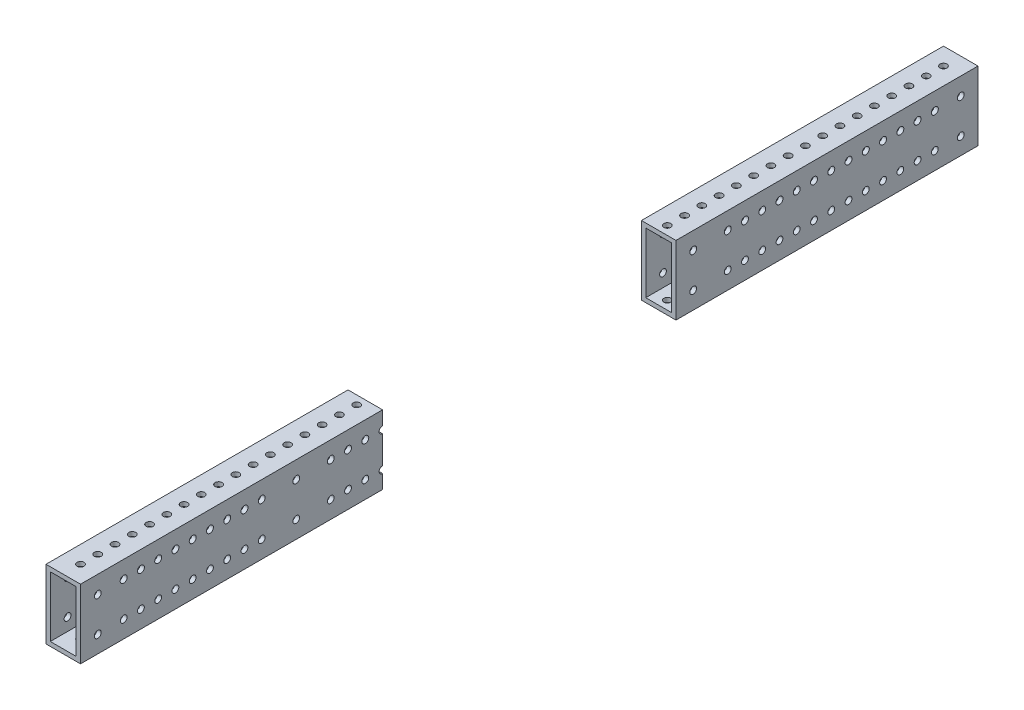
SolidWorks part; units mm, degrees
material "6061-T6 (SS)"
ref_plane "Front Plane" through (0, 0, 0) normal (0, 0, 1) x (1, 0, 0)
ref_plane "Top Plane" through (0, 0, 0) normal (0, 1, 0) x (1, 0, 0)
ref_plane "Right Plane" through (0, 0, 0) normal (1, 0, 0) x (0, 0, -1)
sketch "Sketch1" plane through (0, 0, 0) normal (0, 0, 1) x (1, 0, 0)
  line L0 (-9.525, 22.225) -> (9.525, 22.225)
  line L1 (-12.7, 25.4) -> (12.7, 25.4)
  line L2 (-12.7, 25.4) -> (-12.7, -25.4)
  line L3 (-12.7, -25.4) -> (12.7, -25.4)
  line L4 (12.7, 25.4) -> (12.7, -25.4)
  line L5 (9.525, 22.225) -> (9.525, -22.225)
  line L6 (-9.525, -22.225) -> (9.525, -22.225)
  line L7 (-9.525, 22.225) -> (-9.525, -22.225)
  line L8 (-12.7, 25.4) -> (12.7, -25.4) construction
  line L9 (12.7, 25.4) -> (-12.7, -25.4) construction
  point P5 (0, 0)
  dimension "D1" = 25.4
  dimension "D2" = 50.8
  dimension "D3" = 3.175
extrude "Boss-Extrude1" add sketch "Sketch1" along normal mid plane 660.4
sketch "Sketch2" plane through (0, 25.4, 0) normal (0, 1, 0) x (1, 0, 0)
  line L0 (12.7, -330.2) -> (-12.7, -330.2) construction
  line L1 (-12.7, -330.2) -> (-12.7, 330.2) construction
  line L4 (12.7, 330.2) -> (-12.7, 330.2) construction
  circle A0 centre (0, -317.5) radius 2.5527 construction
  circle A1 centre (25.4, -292.1) radius 2.5527 construction
  circle A2 centre (0, -317.5) radius 2.5527
  circle A3 centre (0, -304.8) radius 2.5527
  circle A4 centre (0, -304.8) radius 2.5527 construction
  circle A5 centre (25.4, -279.4) radius 2.5527 construction
  circle A6 centre (0, -292.1) radius 2.5527
  circle A7 centre (0, -292.1) radius 2.5527 construction
  circle A8 centre (25.4, -266.7) radius 2.5527 construction
  circle A9 centre (0, -279.4) radius 2.5527
  circle A10 centre (0, -279.4) radius 2.5527 construction
  circle A11 centre (25.4, -254) radius 2.5527 construction
  circle A12 centre (0, -266.7) radius 2.5527
  circle A13 centre (0, -266.7) radius 2.5527 construction
  circle A14 centre (25.4, -241.3) radius 2.5527 construction
  circle A15 centre (0, -254) radius 2.5527
  circle A16 centre (0, -254) radius 2.5527 construction
  circle A17 centre (25.4, -228.6) radius 2.5527 construction
  circle A18 centre (0, -241.3) radius 2.5527
  circle A19 centre (0, -241.3) radius 2.5527 construction
  circle A20 centre (25.4, -215.9) radius 2.5527 construction
  circle A21 centre (0, -228.6) radius 2.5527
  circle A22 centre (0, -228.6) radius 2.5527 construction
  circle A23 centre (25.4, -203.2) radius 2.5527 construction
  circle A24 centre (0, -215.9) radius 2.5527
  circle A25 centre (0, -215.9) radius 2.5527 construction
  circle A26 centre (25.4, -190.5) radius 2.5527 construction
  circle A27 centre (0, -203.2) radius 2.5527
  circle A28 centre (0, -203.2) radius 2.5527 construction
  circle A29 centre (25.4, -177.8) radius 2.5527 construction
  circle A30 centre (0, -190.5) radius 2.5527
  circle A31 centre (0, -190.5) radius 2.5527 construction
  circle A32 centre (25.4, -165.1) radius 2.5527 construction
  circle A33 centre (0, -177.8) radius 2.5527
  circle A34 centre (0, -177.8) radius 2.5527 construction
  circle A35 centre (25.4, -152.4) radius 2.5527 construction
  circle A36 centre (0, -165.1) radius 2.5527
  circle A37 centre (0, -165.1) radius 2.5527 construction
  circle A38 centre (25.4, -139.7) radius 2.5527 construction
  circle A39 centre (0, -152.4) radius 2.5527
  circle A40 centre (0, -152.4) radius 2.5527 construction
  circle A41 centre (25.4, -127) radius 2.5527 construction
  circle A42 centre (0, -139.7) radius 2.5527
  circle A43 centre (0, -139.7) radius 2.5527 construction
  circle A44 centre (25.4, -114.3) radius 2.5527 construction
  circle A45 centre (0, -127) radius 2.5527
  circle A46 centre (0, -127) radius 2.5527 construction
  circle A47 centre (25.4, -101.6) radius 2.5527 construction
  circle A48 centre (0, -114.3) radius 2.5527
  circle A49 centre (0, -114.3) radius 2.5527 construction
  circle A50 centre (25.4, -88.9) radius 2.5527 construction
  circle A51 centre (0, -101.6) radius 2.5527
  circle A52 centre (0, -101.6) radius 2.5527 construction
  circle A53 centre (25.4, -76.2) radius 2.5527 construction
  circle A54 centre (0, -88.9) radius 2.5527
  circle A55 centre (0, -88.9) radius 2.5527 construction
  circle A56 centre (25.4, -63.5) radius 2.5527 construction
  circle A57 centre (0, -76.2) radius 2.5527
  circle A58 centre (0, -76.2) radius 2.5527 construction
  circle A59 centre (25.4, -50.8) radius 2.5527 construction
  circle A60 centre (0, -63.5) radius 2.5527
  circle A61 centre (0, -63.5) radius 2.5527 construction
  circle A62 centre (25.4, -38.1) radius 2.5527 construction
  circle A63 centre (0, -50.8) radius 2.5527
  circle A64 centre (0, -50.8) radius 2.5527 construction
  circle A65 centre (25.4, -25.4) radius 2.5527 construction
  circle A66 centre (0, -38.1) radius 2.5527
  circle A67 centre (0, -38.1) radius 2.5527 construction
  circle A68 centre (25.4, -12.7) radius 2.5527 construction
  circle A69 centre (0, -25.4) radius 2.5527
  circle A70 centre (0, -25.4) radius 2.5527 construction
  circle A71 centre (25.4, 0) radius 2.5527 construction
  circle A72 centre (0, -12.7) radius 2.5527
  circle A73 centre (0, -12.7) radius 2.5527 construction
  circle A74 centre (25.4, 12.7) radius 2.5527 construction
  circle A75 centre (0, 0) radius 2.5527
  circle A76 centre (0, 0) radius 2.5527 construction
  circle A77 centre (25.4, 25.4) radius 2.5527 construction
  circle A78 centre (0, 12.7) radius 2.5527
  circle A79 centre (0, 12.7) radius 2.5527 construction
  circle A80 centre (25.4, 38.1) radius 2.5527 construction
  circle A81 centre (0, 25.4) radius 2.5527
  circle A82 centre (0, 25.4) radius 2.5527 construction
  circle A83 centre (25.4, 50.8) radius 2.5527 construction
  circle A84 centre (0, 38.1) radius 2.5527
  circle A85 centre (0, 38.1) radius 2.5527 construction
  circle A86 centre (25.4, 63.5) radius 2.5527 construction
  circle A87 centre (0, 50.8) radius 2.5527
  circle A88 centre (0, 50.8) radius 2.5527 construction
  circle A89 centre (25.4, 76.2) radius 2.5527 construction
  circle A90 centre (0, 63.5) radius 2.5527
  circle A91 centre (0, 63.5) radius 2.5527 construction
  circle A92 centre (25.4, 88.9) radius 2.5527 construction
  circle A93 centre (0, 76.2) radius 2.5527
  circle A94 centre (0, 76.2) radius 2.5527 construction
  circle A95 centre (25.4, 101.6) radius 2.5527 construction
  circle A96 centre (0, 88.9) radius 2.5527
  circle A97 centre (0, 88.9) radius 2.5527 construction
  circle A98 centre (25.4, 114.3) radius 2.5527 construction
  circle A99 centre (0, 101.6) radius 2.5527
  circle A100 centre (0, 101.6) radius 2.5527 construction
  circle A101 centre (25.4, 127) radius 2.5527 construction
  circle A108 centre (0, 127) radius 2.5527 [skipped]
  circle A109 centre (0, 127) radius 2.5527 [skipped]
  circle A110 centre (25.4, 152.4) radius 2.5527 [skipped]
  circle A111 centre (0, 114.3) radius 2.5527 [skipped]
  circle A112 centre (0, 114.3) radius 2.5527 [skipped]
  circle A113 centre (25.4, 139.7) radius 2.5527 [skipped]
  circle A114 centre (25.4, 139.7) radius 2.5527 construction
  circle A115 centre (0, 114.3) radius 2.5527 construction
  circle A116 centre (0, 114.3) radius 2.5527
  circle A117 centre (25.4, 152.4) radius 2.5527 construction
  circle A118 centre (0, 127) radius 2.5527 construction
  circle A119 centre (0, 127) radius 2.5527
  circle A120 centre (25.4, 165.1) radius 2.5527 construction
  circle A121 centre (0, 139.7) radius 2.5527 construction
  circle A122 centre (0, 139.7) radius 2.5527
  circle A123 centre (25.4, 177.8) radius 2.5527 construction
  circle A124 centre (0, 152.4) radius 2.5527 construction
  circle A125 centre (0, 152.4) radius 2.5527
  circle A126 centre (25.4, 190.5) radius 2.5527 construction
  circle A127 centre (0, 165.1) radius 2.5527 construction
  circle A128 centre (0, 165.1) radius 2.5527
  circle A129 centre (25.4, 203.2) radius 2.5527 construction
  circle A130 centre (0, 177.8) radius 2.5527 construction
  circle A131 centre (0, 177.8) radius 2.5527
  circle A132 centre (25.4, 215.9) radius 2.5527 construction
  circle A133 centre (0, 190.5) radius 2.5527 construction
  circle A134 centre (0, 190.5) radius 2.5527
  circle A135 centre (25.4, 228.6) radius 2.5527 construction
  circle A136 centre (0, 203.2) radius 2.5527 construction
  circle A137 centre (0, 203.2) radius 2.5527
  circle A138 centre (25.4, 241.3) radius 2.5527 construction
  circle A139 centre (0, 215.9) radius 2.5527 construction
  circle A140 centre (0, 215.9) radius 2.5527
  circle A141 centre (25.4, 254) radius 2.5527 construction
  circle A142 centre (0, 228.6) radius 2.5527 construction
  circle A143 centre (0, 228.6) radius 2.5527
  circle A144 centre (25.4, 266.7) radius 2.5527 construction
  circle A145 centre (0, 241.3) radius 2.5527 construction
  circle A146 centre (0, 241.3) radius 2.5527
  circle A147 centre (25.4, 279.4) radius 2.5527 construction
  circle A148 centre (0, 254) radius 2.5527 construction
  circle A149 centre (0, 254) radius 2.5527
  circle A150 centre (25.4, 292.1) radius 2.5527 construction
  circle A151 centre (0, 266.7) radius 2.5527 construction
  circle A152 centre (0, 266.7) radius 2.5527
  circle A153 centre (0, 279.4) radius 2.5527
  circle A154 centre (0, 292.1) radius 2.5527
  circle A155 centre (0, 304.8) radius 2.5527
  circle A156 centre (0, 317.5) radius 2.5527
  dimension "D2" = 5.1054
  dimension "D4" = 12.7
  dimension "D9" = 12.7
  dimension "D11" = 12.7
  dimension "D12" = 12.7
  dimension "D1" = 12.7
  dimension "D3" = 12.7
  dimension "D6" = 12.7
  dimension "D7" = 228.6
  dimension "D5" = 36
  dimension "D8" = 14
  dimension "D10" = 5
extrude "Cut-Extrude1" cut sketch "Sketch2" against normal through all
sketch "Sketch4" plane through (12.7, 0, 0) normal (1, 0, 0) x (0, 0, -1)
  line L0 (-330.2, 25.4) -> (330.2, 25.4) construction
  line L1 (-330.2, -25.4) -> (-330.2, 25.4) construction
  line L2 (-330.2, -25.4) -> (330.2, -25.4) construction
  line L3 (-330.2, 25.4) -> (-330.2, -25.4) construction
  line L4 (-134.0934, 25.4) -> (-328.1801, 25.4) construction
  line L5 (-330.2, 25.4) -> (330.2, 25.4) construction
  line L6 (330.2, -25.4) -> (330.2, 25.4) construction
  circle A2 centre (-323.85, -12.7) radius 2.4892 construction
  circle A3 centre (-311.15, -12.7) radius 2.4892 construction
  circle A16 centre (-298.45, -12.7) radius 2.4892
  circle A17 centre (-285.75, -12.7) radius 2.4892
  circle A18 centre (-273.05, -12.7) radius 2.4892
  circle A19 centre (107.95, -12.7) radius 2.4892 construction
  circle A20 centre (120.65, -12.7) radius 2.4892
  circle A21 centre (133.35, -12.7) radius 2.4892 construction
  circle A22 centre (146.05, -12.7) radius 2.4892
  circle A23 centre (158.75, -12.7) radius 2.4892
  circle A24 centre (171.45, -12.7) radius 2.4892
  circle A25 centre (184.15, -12.7) radius 2.4892
  circle A26 centre (196.85, -12.7) radius 2.4892
  circle A27 centre (209.55, -12.7) radius 2.4892
  circle A28 centre (222.25, -12.7) radius 2.4892
  circle A29 centre (234.95, -12.7) radius 2.4892
  circle A30 centre (247.65, -12.7) radius 2.4892
  circle A31 centre (260.35, -12.7) radius 2.4892
  circle A32 centre (273.05, -12.7) radius 2.4892
  circle A33 centre (-323.85, 12.7) radius 2.5527 construction
  circle A34 centre (-311.15, 12.7) radius 2.5527 construction
  circle A35 centre (-260.35, -12.7) radius 2.4892
  circle A36 centre (-247.65, -12.7) radius 2.4892
  circle A37 centre (-234.95, -12.7) radius 2.4892
  circle A38 centre (-222.25, -12.7) radius 2.4892
  circle A39 centre (-209.55, -12.7) radius 2.4892
  circle A40 centre (-196.85, -12.7) radius 2.4892
  circle A41 centre (-184.15, -12.7) radius 2.4892 construction
  circle A42 centre (-171.45, -12.7) radius 2.4892
  circle A43 centre (-158.75, -12.7) radius 2.4892 construction
  circle A44 centre (-146.05, -12.7) radius 2.4892
  circle A45 centre (-133.35, -12.7) radius 2.4892
  circle A46 centre (-120.65, -12.7) radius 2.4892
  circle A47 centre (-107.95, -12.7) radius 2.4892
  circle A48 centre (-95.25, -12.7) radius 2.4892
  circle A49 centre (-82.55, -12.7) radius 2.4892
  circle A50 centre (-69.85, -12.7) radius 2.4892
  circle A51 centre (-57.15, -12.7) radius 2.4892
  circle A52 centre (-44.45, -12.7) radius 2.4892
  circle A53 centre (-31.75, -12.7) radius 2.4892
  circle A54 centre (-19.05, -12.7) radius 2.4892
  circle A55 centre (-6.35, -12.7) radius 2.4892
  circle A56 centre (6.35, -12.7) radius 2.4892
  circle A57 centre (19.05, -12.7) radius 2.4892
  circle A58 centre (31.75, -12.7) radius 2.4892
  circle A59 centre (44.45, -12.7) radius 2.4892
  circle A60 centre (57.15, -12.7) radius 2.4892
  circle A61 centre (69.85, -12.7) radius 2.4892
  circle A62 centre (82.55, -12.7) radius 2.4892
  circle A63 centre (95.25, -12.7) radius 2.4892
  circle A64 centre (-298.45, 12.7) radius 2.5527
  circle A65 centre (-285.75, 12.7) radius 2.5527
  circle A66 centre (-273.05, 12.7) radius 2.5527
  circle A67 centre (-260.35, 12.7) radius 2.5527
  circle A68 centre (-247.65, 12.7) radius 2.5527
  circle A69 centre (-234.95, 12.7) radius 2.5527
  circle A70 centre (-222.25, 12.7) radius 2.5527
  circle A71 centre (-209.55, 12.7) radius 2.5527
  circle A72 centre (-196.85, 12.7) radius 2.5527
  circle A73 centre (-184.15, 12.7) radius 2.5527 construction
  circle A74 centre (-171.45, 12.7) radius 2.5527
  circle A75 centre (-158.75, 12.7) radius 2.5527 construction
  circle A76 centre (-146.05, 12.7) radius 2.5527
  circle A77 centre (-133.35, 12.7) radius 2.5527
  circle A78 centre (-120.65, 12.7) radius 2.5527
  circle A79 centre (-107.95, 12.7) radius 2.5527
  circle A80 centre (-95.25, 12.7) radius 2.5527
  circle A81 centre (-82.55, 12.7) radius 2.5527
  circle A82 centre (-69.85, 12.7) radius 2.5527
  circle A83 centre (-57.15, 12.7) radius 2.5527
  circle A84 centre (-44.45, 12.7) radius 2.5527
  circle A85 centre (-31.75, 12.7) radius 2.5527
  circle A86 centre (-19.05, 12.7) radius 2.5527
  circle A87 centre (-6.35, 12.7) radius 2.5527
  circle A88 centre (6.35, 12.7) radius 2.5527
  circle A89 centre (19.05, 12.7) radius 2.5527
  circle A90 centre (31.75, 12.7) radius 2.5527
  circle A91 centre (44.45, 12.7) radius 2.5527
  circle A92 centre (57.15, 12.7) radius 2.5527
  circle A93 centre (69.85, 12.7) radius 2.5527
  circle A94 centre (82.55, 12.7) radius 2.5527
  circle A95 centre (95.25, 12.7) radius 2.5527
  circle A96 centre (107.95, 12.7) radius 2.5527 construction
  circle A97 centre (120.65, 12.7) radius 2.5527
  circle A98 centre (133.35, 12.7) radius 2.5527 construction
  circle A99 centre (146.05, 12.7) radius 2.5527
  circle A100 centre (158.75, 12.7) radius 2.5527
  circle A101 centre (171.45, 12.7) radius 2.5527
  circle A102 centre (184.15, 12.7) radius 2.5527
  circle A103 centre (196.85, 12.7) radius 2.5527
  circle A104 centre (209.55, 12.7) radius 2.5527
  circle A105 centre (222.25, 12.7) radius 2.5527
  circle A106 centre (234.95, 12.7) radius 2.5527
  circle A107 centre (247.65, 12.7) radius 2.5527
  circle A108 centre (260.35, 12.7) radius 2.5527
  circle A109 centre (273.05, 12.7) radius 2.5527
  circle A110 centre (285.75, 12.7) radius 2.5527
  circle A111 centre (285.75, -12.7) radius 2.4892
  circle A112 centre (298.45, 12.7) radius 2.5527
  circle A113 centre (298.45, -12.7) radius 2.4892
  circle A114 centre (311.15, 12.7) radius 2.5527 construction
  circle A115 centre (311.15, -12.7) radius 2.4892 construction
  circle A116 centre (323.85, 12.7) radius 2.5527 construction
  circle A117 centre (323.85, -12.7) radius 2.4892 construction
  circle A118 centre (-317.5, 12.446) radius 2.5527
  circle A122 centre (-317.5, -12.954) radius 2.5527
  circle A123 centre (317.5, 12.446) radius 2.5527
  circle A124 centre (317.5, -12.954) radius 2.5527
  dimension "D2" = 4.9784
  dimension "D1" = 6.35
  dimension "D8" = 5.1054
  dimension "D9" = 12.7
  dimension "D10" = 6.35
  dimension "D11" = 48
  dimension "D12" = 12.7
  dimension "D13" = 12.7
  dimension "D14" = 12.7
  dimension "D16" = 12.7
  dimension "D17" = 12.954
  dimension "D18" = 5.1054
  dimension "D19" = 12.7
  dimension "D21" = 12.446
  dimension "D22" = 5.1054
  dimension "D23" = 12.954
  dimension "D24" = 12.7
  dimension "D26" = 12.446
  dimension "D3" = 12.7
  dimension "D4" = 12.7
  dimension "D5" = 34
  dimension "D6" = 10
  dimension "D7" = 6
  dimension "D15" = 5
  dimension "D20" = 2
  dimension "D25" = 2
extrude "Cut-Extrude3" cut sketch "Sketch4" against normal through all
sketch "Sketch5" plane through (-12.7, 0, 0) normal (-1, 0, 0) x (0, 0, 1)
  line L0 (330.2, -25.4) -> (-330.2, -25.4) construction
  line L1 (-107.95, -25.4) -> (107.95, -25.4)
  line L2 (-107.95, -25.4) -> (-107.95, 25.4)
  line L3 (-107.95, 25.4) -> (107.95, 25.4)
  line L4 (107.95, -25.4) -> (107.95, 25.4)
  line L5 (330.2, 25.4) -> (-330.2, 25.4) construction
  line L6 (-330.2, 25.4) -> (-330.2, -25.4) construction
  dimension "D1" = 215.9
  dimension "D2" = 222.25
extrude "Cut-Extrude4" cut sketch "Sketch5" against normal through all
